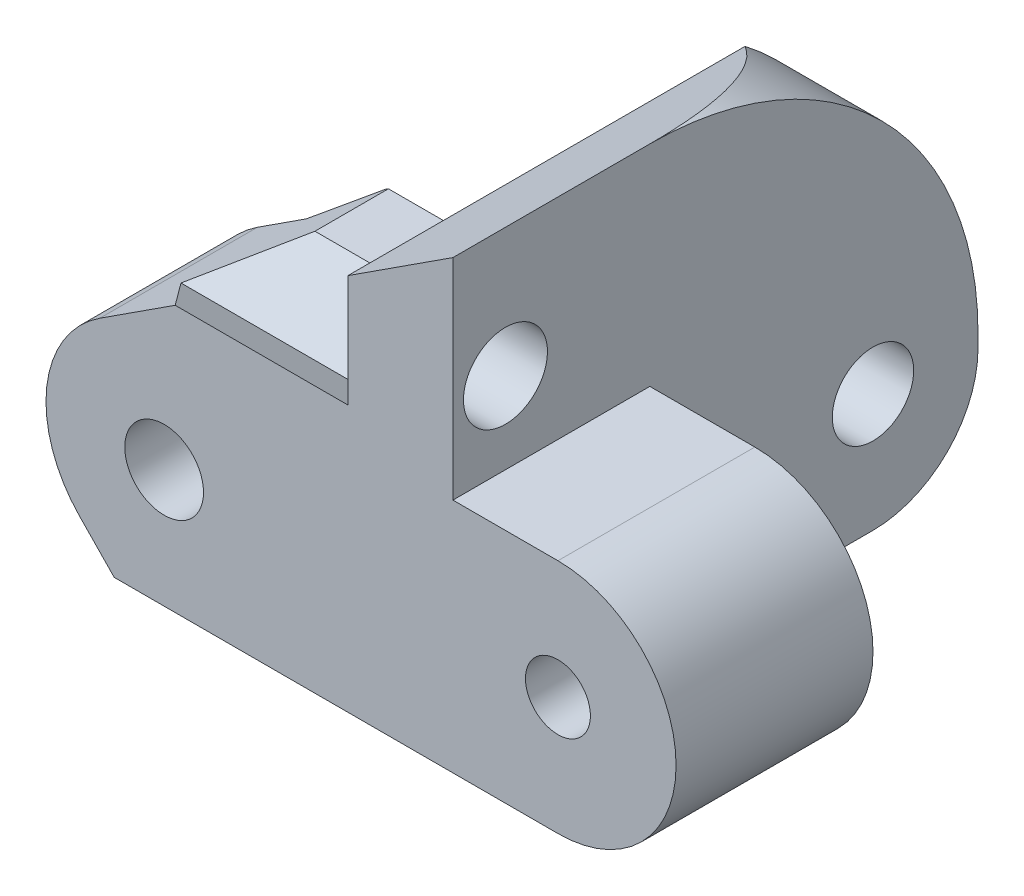
SolidWorks part; units mm, degrees
ref_plane "Front Plane" through (0, 0, 0) normal (0, 0, 1) x (1, 0, 0)
ref_plane "Top Plane" through (0, 0, 0) normal (0, 1, 0) x (1, 0, 0)
ref_plane "Right Plane" through (0, 0, 0) normal (1, 0, 0) x (0, 0, -1)
sketch "Sketch1" plane through (0, 0, 0) normal (0, 0, 1) x (1, 0, 0)
  line L0 (0, 0) -> (9, 0) construction
  line L1 (11, 2) -> (9, 2) construction
  line L2 (11, 12.5) -> (-2.4491, 3.7752)
  line L3 (-3.2272, -3.1361) -> (-1.9018, -4.5)
  line L4 (11, 12.5) -> (11, 4.5)
  line L5 (9, 2) -> (9, -2) construction
  line L6 (9, -2) -> (11, -2) construction
  line L8 (-1.9018, -4.5) -> (15, -4.5)
  line L9 (15, 4.5) -> (11, 4.5)
  line L10 (11, 2) -> (11, -2) construction
  circle A0 centre (0, 0) radius 1.5
  arc A1 (-2.4491, 3.7752) -> (-3.2272, -3.1361) centre (0, 0) ccw
  circle A2 centre (15, 0) radius 1.2368
  arc A3 (15, -4.5) -> (15, 4.5) centre (15, 0) ccw
  dimension "D1" = 3
  dimension "D6" = 3
  dimension "D2" = 4
  dimension "D3" = 11
  dimension "D4" = 2
  dimension "D5" = 15
extrude "Boss-Extrude1" add sketch "Sketch1" along normal blind 20
sketch "Sketch3" plane through (11, 0, 0) normal (1, 0, 0) x (0, 0, -1)
  line L0 (-18, 7.6) -> (-18, -7.6) construction
  line L1 (0, 0) -> (-18, 0) construction
  line L2 (-20, 4.5) -> (-20, 12.5) construction
  line L3 (-20, 12.5) -> (0, 12.5) construction
  circle A0 centre (-18, 7.6) radius 1.6
  circle A1 centre (-18, -7.6) radius 1.6 construction
  dimension "D1" = 3.2
  dimension "D2" = 2
  dimension "D3" = 4.9
extrude "Cut-Extrude3" cut sketch "Sketch3" against normal through all
sketch "Sketch4" plane through (0, 0, 0) normal (0, 0, -1) x (-1, 0, 0)
  line L0 (1.5877, 2.75) -> (1.5877, 5.8624)
  line L1 (-3.1754, 0) -> (-1.5877, -2.75)
  line L2 (-1.5877, -2.75) -> (1.5877, -2.75)
  line L3 (1.5877, -2.75) -> (3.1754, 0) construction
  line L4 (3.1754, 0) -> (1.5877, 2.75) construction
  line L5 (1.5877, 2.75) -> (-1.5877, 2.75)
  line L6 (-1.5877, 2.75) -> (-3.1754, 0)
  line L7 (1.5877, 5.8624) -> (6.5976, 5.8624)
  line L8 (6.5976, 5.8624) -> (6.5976, -6.0998)
  line L9 (6.5976, -6.0998) -> (1.5877, -6.0998)
  line L10 (1.5877, -6.0998) -> (1.5877, -2.75)
  line L11 (0, 0) -> (-15, 0) construction
  line L12 (-7.5, 0) -> (-7.5, 8.2903) construction
  circle A0 centre (0, 0) radius 2.75 construction
  dimension "D1" = 5.5
extrude "Cut-Extrude4" cut sketch "Sketch4" against normal blind 14
sketch "Sketch5" plane through (11, 0, 0) normal (1, 0, 0) x (0, 0, -1)
  line L0 (-15.3, 9.1588) -> (-20, 11.8724) construction
  line L1 (-20, 4.5) -> (-20, 12.5) construction
  line L2 (-15.3, 6.0412) -> (0, 6.0412)
  line L3 (-20.7, 10.5588) -> (-20.7, 7.4412) construction
  line L4 (-20, 5.637) -> (-18, 4.4823)
  line L5 (-18, 4.4823) -> (-15.3, 6.0412)
  line L6 (-15.3, 6.0412) -> (-15.3, 9.1588) construction
  line L7 (0, 4.5) -> (0, 12.5) construction
  line L8 (0, 6.0412) -> (0, 11.3497)
  line L9 (-20, 11.8724) -> (-20, 5.637)
  line L10 (-20, 11.8724) -> (0, 11.3497)
  line L11 (-15.3, 9.1588) -> (0, 11.3497) construction
  line L13 (-18, 10.7177) -> (-21, 8.9856) [skipped]
  line L14 (-15.3, 9.1588) -> (-21, 12.4497) [skipped]
  circle A0 centre (-18, 7.6) radius 2.7 construction
  circle A1 centre (-18, 7.6) radius 1.6 construction
  arc A2 (-15.3, 6.0412) -> (-15.3, 9.1588) centre (-16.2, 7.6) ccw construction
  dimension "D1" = 5.4
extrude "Cut-Extrude5" cut sketch "Sketch5" against normal through all from offset 4 offset against normal yes
ref_plane "Plane1" through (0, 0, 7.5) normal (0, 0, 1) x (1, 0, 0)
sketch "Sketch6" plane through (0, 0, 0) normal (0, 0, -1) x (-1, 0, 0)
  line L0 (-1.0439, 6.0412) -> (-7, 6.0412) construction
  line L1 (-11, 4.5) -> (-19.5, 4.5)
  line L2 (-11, 4.5) -> (-11, -4.5)
  line L3 (-11, -4.5) -> (-19.5, -4.5)
  line L4 (-19.5, 4.5) -> (-19.5, -4.5)
  line L5 (-5.5, 6.0412) -> (4.5, 6.0412)
  line L6 (-5.5, 6.0412) -> (-5.5, -4.5)
  line L7 (-5.5, -4.5) -> (4.5, -4.5)
  line L8 (4.5, 6.0412) -> (4.5, -4.5)
  line L9 (1.5877, -4.5) -> (-15, -4.5) construction
  line L11 (-7, 6.0412) -> (-7, 9.9051) construction
  arc A0 (-15, 4.5) -> (-15, -4.5) centre (-15, 0) ccw construction
  arc A1 (3.2272, -3.1361) -> (2.4491, 3.7752) centre (0, 0) ccw construction
  dimension "D1" = 1.5
extrude "Cut-Extrude6" cut sketch "Sketch6" against normal blind 12.5
chamfer "Chamfer2" distance 2.5 angle 45 2 edges at (-1.5877, -3.625, 12.5) (-1.5877, 3.542, 12.5)
chamfer "Chamfer3" [suppressed] distance 6.5 angle 45
sketch "Sketch7" plane through (0, 0, 12.5) normal (0, 0, -1) x (-1, 0, 0)
  line L1 (-12.2, -1.6166) -> (-12.2, 1.6166)
  line L2 (-12.2, 1.6166) -> (-15, 3.2332)
  line L3 (-15, 3.2332) -> (-17.8, 1.6166)
  line L4 (-17.8, 1.6166) -> (-17.8, -1.6166)
  line L5 (-17.8, -1.6166) -> (-15, -3.2332)
  line L6 (-15, -3.2332) -> (-12.2, -1.6166)
  circle A0 centre (-15, 0) radius 2.8 construction
  circle A1 centre (-15, 0) radius 1.2368 construction
  dimension "D1" = 5.6
extrude "Cut-Extrude7" cut sketch "Sketch7" against normal blind 4.5
sketch "Sketch8" plane through (5.5, 0, 0) normal (-1, 0, 0) x (0, 0, 1)
  line L0 (12.5, 0) -> (0, 0) construction
  line L1 (20, -3.1361) -> (20, 3.7752) construction
  line L2 (20, 12.5) -> (0, 12.5) construction
  line L3 (12.5, 0) -> (12.5, 12.5) construction
  line L4 (12.5, 12.5) -> (0, 12.5)
  line L5 (0, 12.5) -> (0, 0)
  circle A0 centre (4, 0) radius 1.55
  arc A1 (12.5, 12.5) -> (0, 0) centre (12.5, 0) ccw
  dimension "D1" = 3.1
  dimension "D2" = 16
extrude "Cut-Extrude8" cut sketch "Sketch8" against normal through all
fillet "Fillet1" radius 4 1 edges at (8.25, -4.5, 0)
chamfer "Chamfer4" distance 1.8 angle 45 1 edges at (5.5, -1.55, 4)
